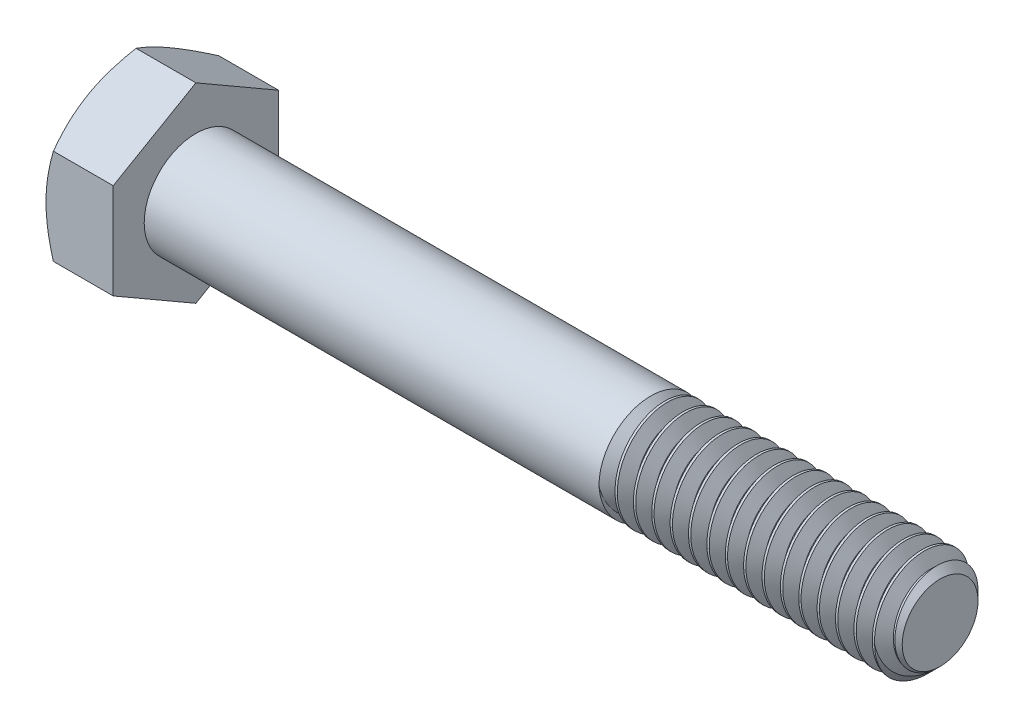
SolidWorks part; units mm, degrees
ref_plane "Front Plane" through (0, 0, 0) normal (0, 0, 1) x (1, 0, 0)
ref_plane "Top Plane" through (0, 0, 0) normal (0, 1, 0) x (1, 0, 0)
ref_plane "Right Plane" through (0, 0, 0) normal (1, 0, 0) x (0, 0, -1)
sketch "Sketch1" plane through (0, 0, 0) normal (0, 0, 1) x (1, 0, 0)
  line L0 (-31.1547, 0) -> (31.1547, 0) construction
  line L1 (31.1547, 3.9688) -> (31.1547, -3.9688) construction
  line L2 (-25.9953, 6.35) -> (-25.9953, -6.35) construction
  line L3 (-31.1547, 6.35) -> (-31.1547, -6.35) construction
  point P9 (-25.9953, 0)
  point P10 (26.2158, -3.9688)
  dimension "Screw Dia" = 7.9375
  dimension "Hex" = 12.7
  dimension "Head Ht" = 5.1594
  dimension "Screw Lenght" = 57.15
  dimension "D1" = 4.9389
ref_plane "Plane2" through (31.1547, 0, 0) normal (1, 0, 0) x (0, 0, -1)
sketch "Sketch5" plane through (31.1547, 0, 0) normal (1, 0, 0) x (0, 0, -1)
  circle A0 centre (0, 0) radius 3.9688
extrude "Boss-Extrude3" add sketch "Sketch5" against normal up to vertex (57.15 mm away) up to point (-25.9953, 0, 0)
sketch "Sketch9" plane through (31.1547, 0, 0) normal (1, 0, 0) x (0, 0, -1)
  circle A1 centre (0, 0) radius 3.9688
  circle A2 centre (0, 0) radius 3.9688
  dimension "D1" = 0
curve "Helix/Spiral1" pitch 1.4111 height 23.6361 turns 16.75 parameters "Pitch"=1.4111
chamfer "Chamfer1" distance 1.0583 angle 45 1 edges at (31.1547, 0, -3.9688)
sketch "Sketch10" plane through (0, 0, 0) normal (0, 0, 1) x (1, 0, 0)
  line L0 (31.1547, 3.9688) -> (31.6839, 3.0522)
  line L1 (31.6839, 3.0522) -> (31.8602, 3.0522)
  line L2 (31.8602, 3.0522) -> (32.3894, 3.9687)
  line L3 (31.1547, 3.9688) -> (32.3894, 3.9687)
  line L4 (31.772, 3.9688) -> (31.772, 3.0522) construction
  line L5 (31.4193, 3.5105) -> (32.1248, 3.5105) construction
  dimension "D1" = 60
  dimension "D2" = 0.1764
  dimension "D3" = 0.7056
sweep "Cut-Sweep1" cut profiles "Sketch10" path "Helix/Spiral1" align with end faces yes
sketch "Sketch11" plane through (0, 0, 0) normal (0, 0, 1) x (1, 0, 0)
  line L0 (-25.9953, 3.9688) -> (-25.9953, 0)
  line L1 (-25.9953, 0) -> (12.8984, 0)
  line L3 (12.8984, 0) -> (8.9297, 3.9688)
  line L4 (-25.9953, 3.9688) -> (8.9297, 3.9688)
  dimension "D1" = 45
  dimension "MIn Thread" = 22.225
revolve "Revolve1" add sketch "Sketch11" angle 360 about L1
sketch "Sketch6" plane through (-25.9953, 0, 0) normal (-1, 0, 0) x (0, 0, 1)
  line L0 (0, 6.35) -> (0, -6.35) construction
  line L1 (6.35, 3.6662) -> (0, 7.3323)
  line L2 (0, 7.3323) -> (-6.35, 3.6662)
  line L3 (-6.35, 3.6662) -> (-6.35, -3.6662)
  line L4 (-6.35, -3.6662) -> (0, -7.3323)
  line L5 (0, -7.3323) -> (6.35, -3.6662)
  line L6 (6.35, -3.6662) -> (6.35, 3.6662)
  circle A0 centre (0, 0) radius 6.35 construction
extrude "Boss-Extrude4" add sketch "Sketch6" along normal up to vertex (5.1594 mm away) up to point (-31.1547, -6.35, 0)
sketch "Sketch7" plane through (-31.1547, 0, 0) normal (-1, 0, 0) x (0, 0, 1)
  circle A0 centre (0, 0) radius 6.35 construction
  circle A1 centre (0, 0) radius 6.35
sketch "Sketch8" plane through (-31.1547, 0, 0) normal (-1, 0, 0) x (0, 0, 1)
  circle A0 centre (0, 0) radius 6.35 construction
  circle A1 centre (0, 0) radius 6.35
extrude "Cut-Extrude3" cut sketch "Sketch8" against normal through all draft 60 flip side to cut
sketch "Sketch12" plane through (-31.1547, 0, 0) normal (-1, 0, 0) x (0, 0, 1)
  line L0 (0, 4.8895) -> (0, 2.7305) construction
  line L1 (0.1905, 4.8895) -> (0.1905, 2.7305)
  line L2 (-0.1905, 4.8895) -> (-0.1905, 2.7305)
  line L3 (0, 3.9688) -> (0, -3.9688) construction
  arc A0 (0.1905, 4.8895) -> (-0.1905, 4.8895) centre (0, 4.8895) ccw
  arc A1 (-0.1905, 2.7305) -> (0.1905, 2.7305) centre (0, 2.7305) ccw
  circle A3 centre (0, 0) radius 2.54 construction
  circle A4 centre (0, 0) radius 5.08 construction
  point P2 (0, 3.81)
  dimension "D1" = 5.08
  dimension "D3" = 10.16
  dimension "D2" = 0.381
extrude "Cut-Extrude4" cut sketch "Sketch12" against normal blind 0.254
pattern_circular "CirPattern1" count 3 over 360 about axis through (0, 0, 0) along (1, 0, 0) of "Cut-Extrude4"
equation "\"D2@Sketch10\" = \"Pitch@Helix/Spiral1\"*.125"
equation "\"D3@Sketch10\" = \"Pitch@Helix/Spiral1\"*.5"
equation "\"D3@Helix/Spiral1\" = \"MIn Thread@Sketch11\"+\"Pitch@Helix/Spiral1\""
equation "\"D1@Chamfer1\" = \"Pitch@Helix/Spiral1\"*.75"
equation "\"D1@Sketch12\" = \"Hex@Sketch1\"*.4"
equation "\"D3@Sketch12\" = \"Hex@Sketch1\"*.8"
equation "\"D2@Sketch12\" = \"Hex@Sketch1\"*.03"
equation "\"D1@Sketch1\" = \"Pitch@Helix/Spiral1\"*3.5"
